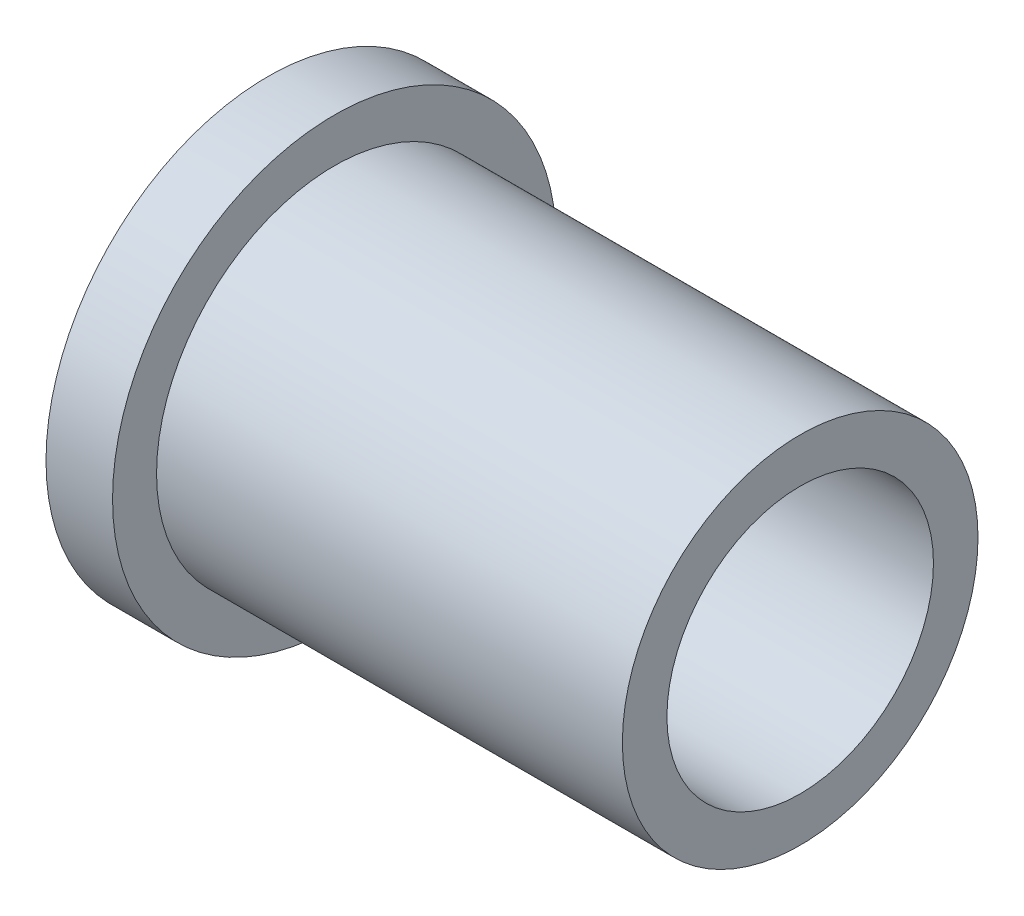
SolidWorks part; units mm, degrees
material "Ductile Iron"
ref_plane "X-Y Datum" through (0, 0, 0) normal (0, 0, 1) x (1, 0, 0)
ref_plane "X-Z Datum" through (0, 0, 0) normal (0, 1, 0) x (1, 0, 0)
ref_plane "Y-Z Datum" through (0, 0, 0) normal (1, 0, 0) x (0, 0, -1)
sketch "Sketch1" plane through (0, 0, 0) normal (1, 0, 0) x (0, 0, -1)
  circle A3 centre (0, 0) radius 15.875
  circle A4 centre (0, 0) radius 12.7254
  circle A5 centre (0, 0) radius 9.5377
  dimension "D1" = 31.75
  dimension "D2" = 25.4508
  dimension "D3" = 19.0754
extrude "Boss-Extrude1" add sketch "Sketch1" along normal blind 4.7625 contours A3 | A5
extrude "Boss-Extrude2" add sketch "Sketch1<3>" along normal blind 38.1 contours A4 | A5
sketch "Sketch1<3>" plane through (0, 0, 0) normal (1, 0, 0) x (0, 0, -1) same geometry as "Sketch1"
